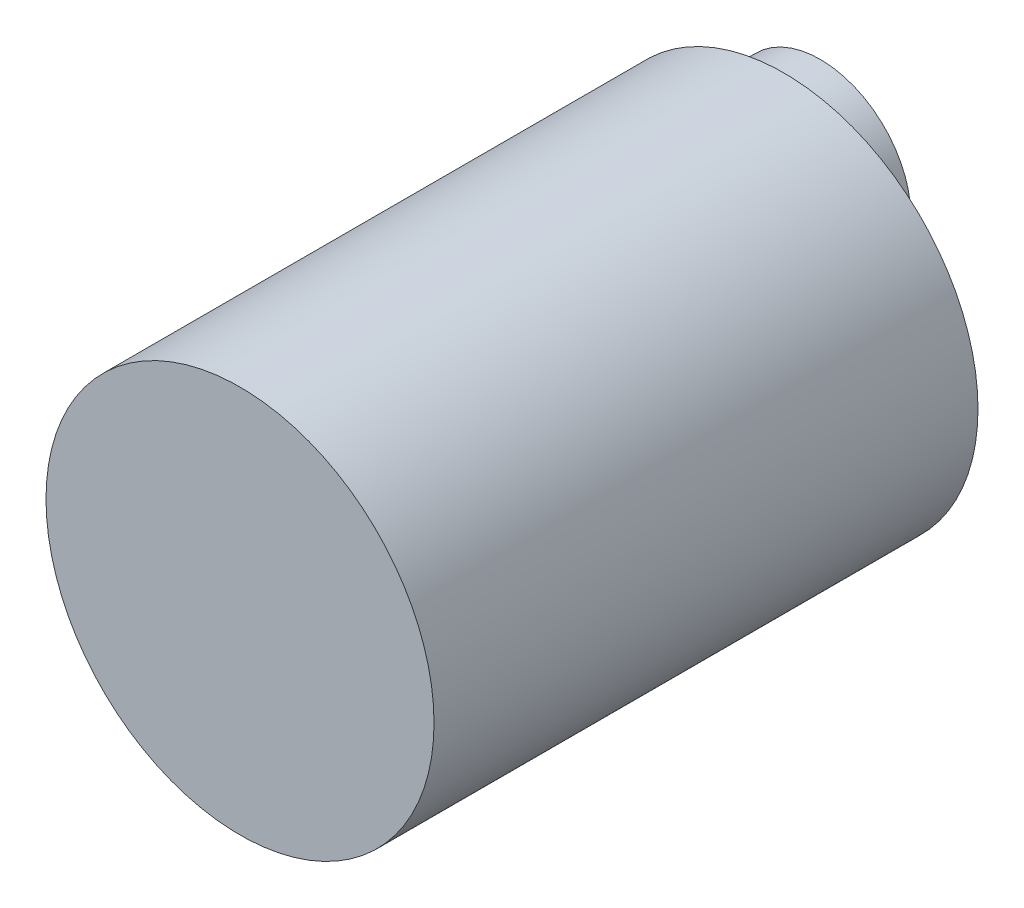
SolidWorks part; units mm, degrees
ref_plane "Front Plane" through (0, 0, 0) normal (0, 0, 1) x (1, 0, 0)
ref_plane "Top Plane" through (0, 0, 0) normal (0, 1, 0) x (1, 0, 0)
ref_plane "Right Plane" through (0, 0, 0) normal (1, 0, 0) x (0, 0, -1)
sketch "Sketch1" plane through (0, 0, 0) normal (0, 0, 1) x (1, 0, 0)
  line L0 (0, 0) -> (0, 13.589) construction
  circle A0 centre (0, 0) radius 13.589
  circle A1 centre (0, 6.7945) radius 6.35
  point P5 (0, 6.7945)
  dimension "D1" = 27.178
  dimension "D2" = 12.7
extrude "Boss-Extrude2" add sketch "Sketch1" along normal blind 38.1 contours A0
extrude "Boss-Extrude3" add sketch "Sketch1<5>" against normal blind 2.54 contours L0 A1 | A1 L0 region at (-2.695, 6.7945, 0) region at (2.695, 6.7945, 0)
sketch "Sketch1<5>" plane through (0, 0, 0) normal (0, 0, 1) x (1, 0, 0) same geometry as "Sketch1"
